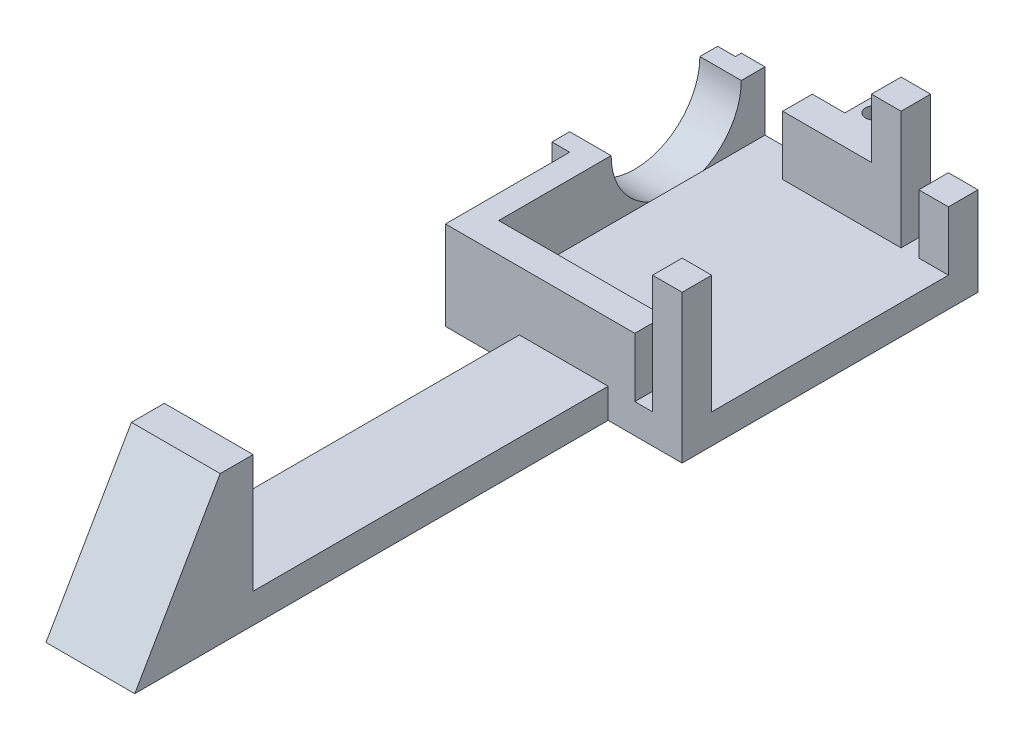
SolidWorks part; units mm, degrees
ref_plane "Front Plane" through (0, 0, 0) normal (0, 0, 1) x (1, 0, 0)
ref_plane "Top Plane" through (0, 0, 0) normal (0, 1, 0) x (1, 0, 0)
ref_plane "Right Plane" through (0, 0, 0) normal (1, 0, 0) x (0, 0, -1)
sketch "Sketch1" plane through (0, 0, 0) normal (0, 1, 0) x (1, 0, 0)
  line L1 (-20, 25) -> (20, 25)
  line L2 (-20, 25) -> (-20, -25)
  line L3 (-20, -25) -> (20, -25)
  line L4 (20, 25) -> (20, -25)
  point P6 (20, 0)
  point P7 (0, 25)
  dimension "D1" = 40
  dimension "D2" = 50
extrude "Boss-Extrude1" add sketch "Sketch1" along normal blind 5
sketch "Sketch3" plane through (0, 5, 0) normal (0, 1, 0) x (1, 0, 0)
  line L0 (20, 25) -> (-20, 25) construction
  line L1 (-8, 25) -> (7, 25)
  line L2 (-8, 25) -> (-8, 20)
  line L3 (-8, 20) -> (7, 20)
  line L4 (7, 25) -> (7, 20)
  line L6 (-20, -25) -> (20, -25) construction
  line L7 (-20, 25) -> (-16, 25)
  line L10 (-16, 25) -> (-16, -20)
  line L11 (20, -25) -> (15, -25)
  line L12 (20, -25) -> (20, -20)
  line L13 (20, -20) -> (15, -20)
  line L14 (15, -25) -> (15, -20)
  line L15 (7, -25) -> (-20, -25)
  line L16 (7, -25) -> (7, -20)
  line L17 (7, -20) -> (-16, -20)
  line L20 (20, 25) -> (15, 25)
  line L21 (20, 25) -> (20, 20)
  line L22 (-20, 25) -> (-20, -25)
  line L23 (7, -20) -> (12, -20)
  line L24 (7, -20) -> (7, -25)
  line L25 (20, 20) -> (15, 20)
  line L26 (7, 20) -> (12, 20)
  line L27 (7, 20) -> (7, 25)
  line L28 (7, 25) -> (12, 25)
  line L29 (12, 20) -> (12, 25)
  line L30 (15, 25) -> (15, 20)
  line L31 (7, -25) -> (12, -25)
  line L32 (12, -20) -> (12, -25)
  line M17 (-20, 25) -> (-20, -25)
  line M18 (-20, -25) -> (20, -25)
  line M19 (20, -25) -> (20, 25)
  line M20 (20, 25) -> (-20, 25)
  dimension "D1" = 8
  dimension "D2" = 15
  dimension "D3" = 4
  dimension "D4" = 5
  dimension "D5" = 5
  dimension "D7" = 5
extrude "Boss-Extrude5" add sketch "Sketch3" along normal blind 20 contours L14 L13 M18 M19 | L26 L29 L4 M20 region at (9.5, 5, -22.5) region at (17.5, 5, 22.5)
extrude "Boss-Extrude6" add sketch "Sketch3<3>" along normal blind 10 contours L4 L2 L3 M20 | L16 L17 L10 M20 M17 M18 | L21 L20 L30 L25 | L24 L23 L32 L31 region at (-0.5, 5, -22.5) region at (-16.5682, 5, -2.5)
sketch "Sketch3<3>" plane through (0, 5, 0) normal (0, 1, 0) x (1, 0, 0) same geometry as "Sketch3"
sketch "Sketch8" plane through (-20, 0, 0) normal (-1, 0, 0) x (0, 0, 1)
  line L0 (-25, 15) -> (25, 15) construction
  line L1 (1, 15) -> (-21, 15)
  arc A0 (-21, 15) -> (1, 15) centre (-10, 15) ccw
  dimension "D1" = 22
  dimension "D2" = 4
extrude "Cut-Extrude3" cut sketch "Sketch8" against normal blind 4
sketch "Sketch10" plane through (-20, 0, 0) normal (-1, 0, 0) x (0, 0, 1)
  line L0 (1, 15) -> (4, 15)
  line L1 (1, 15) -> (25, 15) construction
  line L2 (4, 15) -> (4, 0)
  line L3 (-25, 0) -> (25, 0) construction
  line L4 (4, 0) -> (-24, 0)
  line L5 (-24, 0) -> (-24, 15)
  line L6 (-25, 15) -> (-21, 15) construction
  line L7 (-24, 15) -> (-21, 15)
  arc A0 (-21, 15) -> (1, 15) centre (-10, 15) ccw
  dimension "D2" = 11
  dimension "D1" = 3
extrude "Boss-Extrude9" add sketch "Sketch10" along normal blind 3
sketch "Sketch12" plane through (0, 0, -25) normal (0, 0, -1) x (-1, 0, 0)
  line L0 (-7, 15) -> (8, 15) construction
  line L1 (-2.5, 15) -> (2.5, 15)
  line L2 (-2.5, 15) -> (-2.5, 10)
  line L3 (-2.5, 10) -> (2.5, 10)
  line L4 (2.5, 15) -> (2.5, 10)
  point P6 (0, 10)
  dimension "D1" = 5
  dimension "D2" = 5
extrude "Boss-Extrude10" add sketch "Sketch12" along normal blind 5
sketch "Sketch13" plane through (0, 10, 0) normal (0, -1, 0) x (1, 0, 0)
  line L0 (20, -25) -> (-20, -25) construction
  line L1 (-2.5, -30) -> (-2.5, -25) construction
  circle A0 centre (0, -27.5) radius 1.5
  point P4 (0, -25)
  point P7 (-2.5, -27.5)
  dimension "D1" = 3
extrude "Cut-Extrude4" cut sketch "Sketch13" against normal blind 5
sketch "Sketch14" plane through (0, 0, 25) normal (0, 0, 1) x (1, 0, 0)
  line L0 (-20, 0) -> (20, 0) construction
  line L1 (7.5, 0) -> (-7.5, 0)
  line L2 (7.5, 0) -> (7.5, 5)
  line L3 (7.5, 5) -> (-7.5, 5)
  line L4 (-7.5, 0) -> (-7.5, 5)
  point P6 (0, 5)
  dimension "D1" = 5
  dimension "D2" = 15
extrude "Boss-Extrude11" add sketch "Sketch14" along normal blind 80
sketch "Sketch15" plane through (0, 5, 0) normal (0, 1, 0) x (1, 0, 0)
  line L0 (7.5, -105) -> (7.5, -25) construction
  line L1 (-7.5, -105) -> (7.5, -105)
  line L2 (-7.5, -105) -> (-7.5, -85)
  line L3 (-7.5, -85) -> (7.5, -85)
  line L4 (7.5, -105) -> (7.5, -85)
  dimension "D1" = 20
extrude "Boss-Extrude13" add sketch "Sketch15" along normal blind 20
sketch "Sketch18" plane through (-7.5, 0, 0) normal (-1, 0, 0) x (0, 0, 1)
  line L0 (105, 0) -> (90.5662, 25)
  line L1 (90.5662, 25) -> (105, 25)
  line L2 (105, 25) -> (105, 0)
  dimension "D1" = 30
extrude "Cut-Extrude7" cut sketch "Sketch18" against normal blind 15
